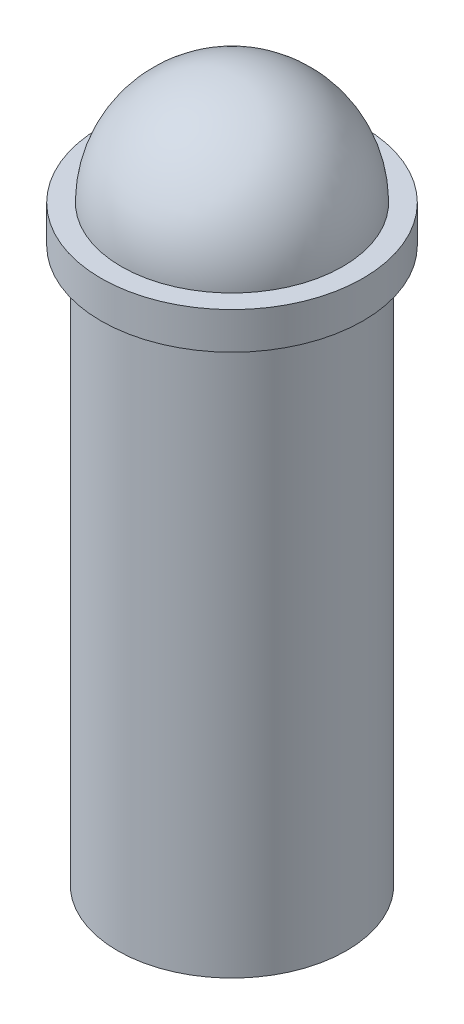
SolidWorks part; units mm, degrees
ref_plane "Front Plane" through (0, 0, 0) normal (0, 0, 1) x (1, 0, 0)
ref_plane "Top Plane" through (0, 0, 0) normal (0, 1, 0) x (1, 0, 0)
ref_plane "Right Plane" through (0, 0, 0) normal (1, 0, 0) x (0, 0, -1)
sketch "Sketch1" plane through (0, 0, 0) normal (0, 1, 0) x (1, 0, 0)
  circle A0 centre (0, 0) radius 3.55
  dimension "D1" = 7.1
extrude "Boss-Extrude1" add sketch "Sketch1" along normal blind 1
sketch "Sketch2" plane through (0, 0, 0) normal (1, 0, 0) x (0, 0, -1)
  line L0 (0, 1) -> (0, 4)
  line L1 (3.55, 1) -> (-3.55, 1) construction
  line L2 (3, 1) -> (0, 1)
  line L3 (0, 4) -> (-6.0686, 4) construction
  line L4 (3, 1) -> (3, -1.2713) construction
  arc A0 (0, 4) -> (3, 1) centre (0, 1) cw
  dimension "D1" = 4
ref_axis "Axis1" through (0, 1, 0) along (0, -1, 0)
revolve "Revolve1" add sketch "Sketch2" angle 360 about axis through (0, 1, 0) along (0, -1, 0)
sketch "Sketch3" plane through (0, 0, 0) normal (0, -1, 0) x (1, 0, 0)
  circle A0 centre (0, 0) radius 3.1
  dimension "D1" = 6.2
extrude "Boss-Extrude2" add sketch "Sketch3" along normal blind 15
ref_axis "Axis2" through (0, -15, 0) along (0, 1, 0)
ref_plane "Plane2" through (0, 0, 0) normal (0.7071, 0, 0.7071) x (0.7071, 0, -0.7071)
ref_plane "Plane1" through (3.1, 0, 0) normal (1, 0, 0) x (0, 0, -1)
ref_plane "Plane3" through (3.1, 0, 0) normal (1, 0, 0) x (0, 0, -1)
